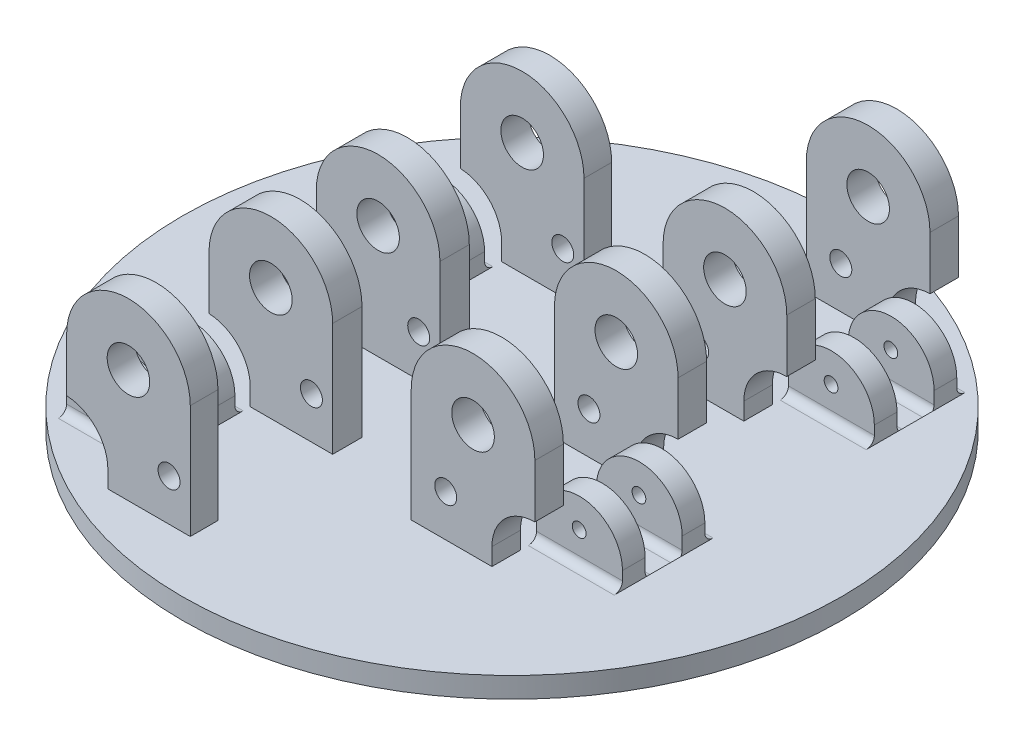
SolidWorks part; units mm, degrees
ref_plane "前视基准面" through (0, 0, 0) normal (0, 0, 1) x (1, 0, 0)
ref_plane "上视基准面" through (0, 0, 0) normal (0, 1, 0) x (1, 0, 0)
ref_plane "右视基准面" through (0, 0, 0) normal (1, 0, 0) x (0, 0, -1)
sketch "草图1" plane through (0, 0, 0) normal (0, 1, 0) x (1, 0, 0)
  line L4 (-45, -14.75) -> (46.6034, -14.75) construction
  circle A0 centre (-27, -5.58) radius 1
  circle A13 centre (-27, -42.25) radius 1
  circle A14 centre (27, 12.75) radius 1
  circle A15 centre (27, -23.92) radius 1
  circle A16 centre (0, -14.75) radius 48
  dimension "D13" = 36.67
  dimension "D14" = 2
  dimension "D16" = 2
  dimension "D2" = 27
  dimension "D15" = 2
  dimension "D17" = 2
  dimension "D6" = 18.34
  dimension "D3" = 27
  dimension "D4" = 27
  dimension "D5" = 27
  dimension "D7" = 9.17
extrude "凸台-拉伸1" add sketch "草图1" along normal blind 2.5 contours A14 A0 region at (0, 0, 14.75)
sketch "草图11" plane through (0, 2.5, 0) normal (0, 1, 0) x (1, 0, 0)
  line L1 (-25, 6.759) -> (-7, 6.759)
  line L2 (-25, 6.759) -> (-25, -18.241)
  line L3 (-25, -18.241) -> (-7, -18.241)
  line L4 (-7, 6.759) -> (-7, -18.241)
  line L5 (-25, -29.589) -> (-7, -29.589)
  line L6 (-25, -29.589) -> (-25, -54.589)
  line L7 (-25, -54.589) -> (-7, -54.589)
  line L8 (-7, -29.589) -> (-7, -54.589)
  line L9 (25, 25.25) -> (7, 25.25)
  line L10 (25, 25.25) -> (25, 0.25)
  line L11 (25, 0.25) -> (7, 0.25)
  line L12 (7, 25.25) -> (7, 0.25)
  line L13 (25, -11.42) -> (7, -11.42)
  line L14 (25, -11.42) -> (25, -36.42)
  line L15 (25, -36.42) -> (7, -36.42)
  line L16 (7, -11.42) -> (7, -36.42)
  line L17 (-25, 2.42) -> (-30, 2.42)
  line L18 (-25, 2.42) -> (-25, -13.58)
  line L19 (-25, -13.58) -> (-30, -13.58)
  line L20 (-30, 2.42) -> (-30, -13.58)
  line L21 (25, 20.75) -> (30, 20.75)
  line L22 (25, 20.75) -> (25, 4.75)
  line L23 (25, 4.75) -> (30, 4.75)
  line L24 (30, 20.75) -> (30, 4.75)
  line L25 (25, -15.92) -> (30, -15.92)
  line L26 (25, -15.92) -> (25, -31.92)
  line L27 (25, -31.92) -> (30, -31.92)
  line L28 (30, -15.92) -> (30, -31.92)
  line L29 (-25, -34.25) -> (-30, -34.25)
  line L30 (-25, -34.25) -> (-25, -50.25)
  line L31 (-25, -50.25) -> (-30, -50.25)
  line L32 (-30, -34.25) -> (-30, -50.25)
  circle A0 centre (-27, -5.58) radius 1 construction
  circle A1 centre (-27, -42.25) radius 1 construction
  circle A2 centre (27, -23.92) radius 1 construction
  circle A3 centre (27, 12.75) radius 1 construction
  dimension "D1" = 25
  dimension "D2" = 25
  dimension "D3" = 25
  dimension "D4" = 25
  dimension "D5" = 16
  dimension "D6" = 16
  dimension "D7" = 16
  dimension "D8" = 16
  dimension "D9" = 12.5
  dimension "D10" = 8
  dimension "D11" = 12.5
  dimension "D12" = 8
  dimension "D13" = 12.5
  dimension "D14" = 8
  dimension "D15" = 12.5
  dimension "D16" = 8
  dimension "D17" = 18
  dimension "D18" = 5
  dimension "D19" = 18
  dimension "D20" = 5
  dimension "D21" = 18
  dimension "D22" = 5
  dimension "D23" = 5
  dimension "D24" = 18
  dimension "D25" = 3
  dimension "D26" = 3
  dimension "D27" = 3
  dimension "D28" = 3
extrude "凸台-拉伸13" add sketch "草图11" along normal blind 26 contours L4 L1 L2 L3 | L9 L12 L11 L10 | L13 L16 L15 L14 | L8 L5 L6 L7 region at (-16, 2.5, 5.741) region at (-16, 2.5, 42.089) region at (16, 2.5, -12.75) region at (16, 2.5, 23.92)
sketch "草图12" plane through (0, 0, -6.759) normal (0, 0, -1) x (-1, 0, 0)
  line L0 (25, 19.5) -> (25, 11.745)
  line L1 (7, 28.5) -> (7, 2.5) construction
  line L2 (19, 2.5) -> (25, 2.5)
  line L3 (25, 28.5) -> (25, 2.5) construction
  line L4 (7, 19.5) -> (7, 2.5)
  line L5 (7, 2.5) -> (19, 2.5)
  line L6 (25, 11.745) -> (25, 19.5)
  line L7 (7, 2.5) -> (19, 2.5)
  line L8 (19, 2.5) -> (19, 5.5)
  line L10 (25, 2.5) -> (31.5, 2.5)
  line L11 (31.5, 2.5) -> (31.5, 5.5)
  arc A0 (7, 19.5) -> (25, 19.5) centre (16, 19.5) cw
  circle A1 centre (16, 19.5) radius 3.1
  arc A2 (19, 5.5) -> (31.5, 5.5) centre (25.25, 5.5) cw
  circle A3 centre (10.09, 9.09) radius 1.6
  line M2 (7, 2.5) -> (25, 2.5)
  line M3 (25, 2.5) -> (25, 28.5)
  line M4 (25, 28.5) -> (7, 28.5)
  line M5 (7, 28.5) -> (7, 2.5)
  dimension "D1" = 3
  dimension "D2" = 3.2
  dimension "D3" = 10.41
  dimension "D4" = 5.91
  dimension "D5" = 12
  dimension "D6" = 3
  dimension "D7" = 12.5
extrude "切除-拉伸19" cut sketch "草图12" against normal through all contours A0 M5 M4 region at (-9.0103, 26.4897, -6.759)
extrude "切除-拉伸23" cut sketch "草图12<9>" against normal blind 26 contours A0 M4 M3 region at (-22.9897, 26.4897, -6.759)
sketch "草图12<9>" plane through (0, 0, -6.759) normal (0, 0, -1) x (-1, 0, 0) same geometry as "草图12"
extrude "切除-拉伸24" cut sketch "草图12<10>" against normal through all contours A1 | A3 region at (-16, 19.5, -6.759) region at (-10.09, 9.09, -6.759)
sketch "草图12<10>" plane through (0, 0, -6.759) normal (0, 0, -1) x (-1, 0, 0) same geometry as "草图12"
extrude "切除-拉伸25" cut sketch "草图12<11>" against normal through all contours A2 L8 M2 M3 region at (-22.2854, 6.5506, -6.759)
sketch "草图12<11>" plane through (0, 0, -6.759) normal (0, 0, -1) x (-1, 0, 0) same geometry as "草图12"
sketch "草图13" plane through (0, 0, 54.589) normal (0, 0, 1) x (1, 0, 0)
  line L0 (-25, 28.5) -> (-25, 11.745) construction
  line L1 (-25, 19.5) -> (-25, 28.5)
  line L2 (-25, 28.5) -> (-16, 28.5)
  arc A0 (-16, 28.5) -> (-25, 19.5) centre (-16, 19.5) ccw
extrude "切除-拉伸26" cut sketch "草图13" against normal through all
sketch "草图16" plane through (-25, 0, 0) normal (-1, 0, 0) x (0, 0, 1)
  line L0 (5.6201, 10.245) -> (5.6201, 31.9219) construction
  line L1 (18.1201, 10.245) -> (-6.8799, 10.245) construction
  line L2 (18.241, 2.5) -> (-6.759, 2.5) construction
  line L3 (13.9701, 10.245) -> (13.9701, 31.9219)
  line L4 (13.9701, 31.9219) -> (-2.7299, 31.9219)
  line L5 (-2.7299, 31.9219) -> (-2.7299, 10.245)
  line L6 (13.9701, 2.5) -> (-2.7299, 2.5)
  line L7 (-2.7299, 10.245) -> (-2.7299, 2.5)
  line L9 (13.9701, 10.245) -> (13.9701, 2.5)
sketch "草图17" plane through (-25, 0, 0) normal (-1, 0, 0) x (0, 0, 1)
  line L1 (54.7099, 10.245) -> (29.7099, 10.245) construction
  line L3 (50.5599, 10.245) -> (50.5599, 33.0392)
  line L4 (50.5599, 33.0392) -> (33.8599, 33.0392)
  line L5 (33.8599, 33.0392) -> (33.8599, 10.245)
  line L8 (33.8599, 10.245) -> (33.8599, 2.5)
  line L9 (33.8599, 2.5) -> (50.5599, 2.5)
  line L10 (50.5599, 2.5) -> (50.5599, 10.245)
extrude "切除-拉伸31" cut sketch "草图17" against normal up to next
extrude "切除-拉伸30" cut sketch "草图16" against normal up to next
sketch "草图19" plane through (0, 0, -6.759) normal (0, 0, -1) x (-1, 0, 0)
  line L0 (19, 5.5) -> (19, 2.5)
  line L1 (31.5, 5.5) -> (31.5, 2.5)
  line L2 (31.5, 2.5) -> (19, 2.5)
  arc A0 (25, 11.745) -> (19, 5.5) centre (25.25, 5.5) ccw construction
  arc A1 (25, 11.745) -> (19, 5.5) centre (25.25, 5.5) ccw
  arc A2 (25, 11.745) -> (31.5, 5.5) centre (25.25, 5.5) cw
ref_plane "基准面1" through (0, 0, 5.741) normal (0, 0, -1) x (-1, 0, 0)
sketch "草图20" plane through (0, 0, 5.741) normal (0, 0, -1) x (-1, 0, 0)
  line L0 (31.5, 2.5) -> (19, 2.5) construction
  line L1 (31.5, 5.5) -> (31.5, 2.5) construction
  line L2 (19, 5.5) -> (19, 2.5) construction
  line L3 (31.5, 2.5) -> (19, 2.5)
  line L4 (31.5, 5.5) -> (31.5, 2.5)
  line L5 (19, 5.5) -> (19, 2.5)
  arc A0 (31.5, 5.5) -> (25, 11.745) centre (25.25, 5.5) ccw construction
  arc A1 (25, 11.745) -> (19, 5.5) centre (25.25, 5.5) ccw construction
  arc A2 (31.5, 5.5) -> (25, 11.745) centre (25.25, 5.5) ccw
  arc A3 (25, 11.745) -> (19, 5.5) centre (25.25, 5.5) ccw
  circle A4 centre (25.3145, 7.499) radius 1
  dimension "D1" = 2
extrude "凸台-拉伸18" add sketch "草图20" along normal mid plane 12
sketch "草图21" plane through (-31.5, 0, 0) normal (-1, 0, 0) x (0, 0, 1)
  line L0 (-0.259, 2.5) -> (11.741, 2.5) construction
  line L1 (8.4951, 2.5) -> (3.0951, 2.5)
  line L2 (8.4951, 2.5) -> (8.4951, 20.5257)
  line L3 (8.4951, 20.5257) -> (3.0951, 20.5257)
  line L4 (3.0951, 2.5) -> (3.0951, 20.5257)
  dimension "D1" = 5.4
extrude "切除-拉伸33" cut sketch "草图21" against normal up to next
ref_plane "基准面2" through (0, 0, 23.915) normal (0, 0, -1) x (-1, 0, 0)
mirror "镜向2" about plane through (0, 0, 23.915) normal (0, 0, -1) of "凸台-拉伸18"
mirror "镜向5" about plane through (0, 0, 23.915) normal (0, 0, -1) of "切除-拉伸33"
sketch "草图24" plane through (0, 0, -25.25) normal (0, 0, -1) x (-1, 0, 0)
  line L0 (-25, 28.5) -> (-25, 19.5)
  line L1 (-25, 28.5) -> (-25, 2.5) construction
  line L2 (-25, 19.5) -> (-25, 28.5)
  line L3 (-7, 28.5) -> (-7, 2.5) construction
  line L4 (-18.75, 5.5127) -> (-18.75, 2.5)
  line L7 (-7, 28.5) -> (-7, 19.5)
  line L11 (-25, 2.5) -> (-7, 2.5) construction
  line L12 (48, 2.5) -> (-48, 2.5) construction
  line L13 (-31.25, 5.5) -> (-31.25, 2.5)
  line L14 (-18.75, 2.5) -> (-31.25, 2.5)
  arc A0 (-25, 19.5) -> (-7, 19.5) centre (-16, 19.5) cw
  circle A1 centre (-16, 19.5) radius 3.1
  arc A2 (-31.25, 5.5) -> (-18.75, 5.5127) centre (-25, 5.5) cw
  circle A6 centre (-12.0207, 9.09) radius 1.6
  line M1 (-25, 2.5) -> (-7, 2.5)
  line M2 (-7, 2.5) -> (-7, 28.5)
  line M3 (-7, 28.5) -> (-25, 28.5)
  line M4 (-25, 28.5) -> (-25, 2.5)
  dimension "D1" = 3
  dimension "D3" = 6.25
extrude "切除-拉伸35" cut sketch "草图24" against normal through all contours A0 M4 M3 | A0 M3 M2 | A1 | A6 | A2 L4 M4 M1 region at (22.9897, 26.4897, -25.25) region at (9.0103, 26.4897, -25.25) region at (22.1682, 6.5774, -25.25) region at (16, 19.5, -25.25) region at (12.0207, 9.09, -25.25)
sketch "草图26" plane through (25, 0, 0) normal (1, 0, 0) x (0, 0, -1)
  line L0 (33.25, 2.5) -> (-62.75, 2.5) construction
  line L1 (-15.57, 2.5) -> (-32.27, 2.5)
  line L2 (-15.57, 2.5) -> (-15.57, 33.9045)
  line L3 (-15.57, 33.9045) -> (-32.27, 33.9045)
  line L4 (-32.27, 2.5) -> (-32.27, 33.9045)
  dimension "D1" = 16.7
extrude "切除-拉伸40" cut sketch "草图26" against normal up to surface (18 mm away) up to face at (7, 11, 23.92)
ref_plane "基准面5" through (0, 0, 23.92) normal (0, 0, -1) x (-1, 0, 0)
sketch "草图27" plane through (0, 0, 23.92) normal (0, 0, -1) x (-1, 0, 0)
  line L2 (-31.25, 5.5) -> (-31.25, 2.5)
  line L3 (-31.25, 2.5) -> (-18.75, 2.5)
  line L4 (-18.75, 2.5) -> (-18.75, 5.5127)
  line L9 (48, 2.5) -> (-48, 2.5) construction
  arc A1 (-18.75, 5.5127) -> (-25, 11.75) centre (-25, 5.5) ccw construction
  arc A2 (-18.75, 5.5127) -> (-25, 11.75) centre (-25, 5.5) ccw
  arc A3 (-25, 11.75) -> (-31.25, 5.5) centre (-25, 5.5) ccw
  circle A4 centre (-24.9508, 7.4994) radius 1
  circle A5 centre (-16, 19.5) radius 3.1
  circle A6 centre (-16, 19.5) radius 3.1
  dimension "D1" = 0
  dimension "D2" = 2
extrude "凸台-拉伸20" add sketch "草图27" along normal mid plane 12 contours L2 A4 region at (29.3095, 9.8095, 23.92)
sketch "草图28" plane through (33.4307, 0, 0) normal (1, 0, 0) x (0, 0, -1)
  line L0 (-23.92, 2.5) -> (-21.22, 2.5)
  line L1 (-17.92, 2.5) -> (-29.92, 2.5) construction
  line L2 (-26.62, 2.5) -> (-26.62, 12.9642)
  line L3 (-26.62, 12.9642) -> (-21.22, 12.9642)
  line L4 (-21.22, 12.9642) -> (-21.22, 2.5)
  line L5 (-26.62, 2.5) -> (-23.92, 2.5)
  dimension "D1" = 2.7
  dimension "D2" = 2.7
extrude "切除-拉伸41" cut sketch "草图28" against normal up to next
ref_plane "基准面6" through (0, 0, 5.585) normal (0, 0, -1) x (-1, 0, 0)
sketch "草图29" plane through (7, 0, 0) normal (-1, 0, 0) x (0, 0, 1)
  line L0 (-12.75, 19.5) -> (-12.75, 1.9724) construction
  line L1 (-0.25, 19.5) -> (-25.25, 19.5) construction
  line L2 (-12.75, 2.5) -> (-21.1, 2.5)
  line L3 (-25.25, 2.5) -> (-0.25, 2.5) construction
  line L4 (-21.1, 2.5) -> (-21.1, 15.8913)
  line L5 (-21.1, 15.8913) -> (-21.1, 43.9288)
  line L6 (-4.4, 15.8913) -> (-4.4, 2.5)
  line L7 (-25.25, 2.5) -> (-0.25, 2.5) construction
  line L8 (-4.4, 2.5) -> (-12.75, 2.5)
  line L9 (-21.1, 43.9288) -> (-4.4, 43.9288)
  line L10 (-4.4, 43.9288) -> (-4.4, 15.8913)
  dimension "D1" = 16.7
  dimension "D2" = 8.35
extrude "切除-拉伸42" cut sketch "草图29" against normal up to surface (18 mm away) up to face at (25, 15.625, -12.75)
mirror "镜向11" about plane through (0, 0, 5.585) normal (0, 0, -1) of "切除-拉伸41", "凸台-拉伸20"
sketch "草图34" plane through (0, 0, 0) normal (0, -1, 0) x (1, 0, 0)
  line L0 (0, 62.75) -> (0, -14.4275) construction
  line L1 (0, 14.75) -> (14.0338, 60.6526) construction
  line L2 (0, 14.75) -> (-14.0338, -31.1526) construction
  line L10 (0, 14.75) -> (0, 16.25)
  line L12 (0, 14.75) -> (-45.9026, 28.7838) construction
  line L19 (14.6833, 1.8953) -> (-19.3612, 12.3038)
  line L20 (14.6833, 1.8953) -> (15.5604, 4.7643)
  line L21 (-19.3612, 12.3038) -> (-18.4841, 15.1727)
  line L22 (15.5604, 4.7643) -> (-18.4841, 15.1727)
  line L23 (14.6833, 1.8953) -> (-18.4841, 15.1727) construction
  line L24 (-19.3612, 12.3038) -> (15.5604, 4.7643) construction
  line L25 (-28.1323, -16.3854) -> (5.9121, -26.7938)
  line L26 (-28.1323, -16.3854) -> (-29.0095, -19.2543)
  line L27 (5.9121, -26.7938) -> (5.035, -29.6627)
  line L28 (-29.0095, -19.2543) -> (5.035, -29.6627)
  line L29 (-28.1323, -16.3854) -> (5.035, -29.6627) construction
  line L30 (5.9121, -26.7938) -> (-29.0095, -19.2543) construction
  circle A0 centre (0, 14.75) radius 48 construction
  dimension "D1" = 17
  dimension "D2" = 7
  dimension "D3" = 1.5
  dimension "D4" = 30
  dimension "D5" = 35.6
  dimension "D6" = 3
  dimension "D8" = 35.6
  dimension "D9" = 3
extrude "凸台-拉伸21" add sketch "草图34" along normal blind 11.5 contours L20 L22 L21 L19 | L26 L28 L27 L25 region at (-1.9004, 0, 8.534) region at (-11.5487, 0, -23.024)
sketch "草图35" plane through (-7.8632, 0, -25.7193) normal (-0.2924, 0, -0.9563) x (-0.9563, 0, 0.2924)
  line L1 (22.1125, -11.5) -> (-13.4875, -11.5) construction
  line L2 (4.3125, -11.5) -> (4.3125, 0) construction
  line L3 (-13.4875, -11.5) -> (-13.4875, 0) construction
  line L4 (22.1125, 0) -> (-13.4875, 0) construction
  circle A0 centre (19.3125, -9.1) radius 1.4
  circle A1 centre (12.8125, -2.8) radius 1.4
  circle A4 centre (-4.1875, -2.8) radius 1.4
  circle A5 centre (-10.6875, -9.1) radius 1.4
  dimension "D1" = 2.8
  dimension "D2" = 2.8
  dimension "D3" = 6.3
  dimension "D4" = 6.5
extrude "切除-拉伸43" cut sketch "草图35" against normal through all
sketch "草图36" plane through (2.6622, 0, 8.7076) normal (0.2924, 0, 0.9563) x (0.9563, 0, -0.2924)
  line L0 (-10.6125, 0) -> (-10.6125, -5.6)
  line L1 (13.4875, 0) -> (-22.1125, 0) construction
  line L2 (-10.6125, -5.6) -> (-16.5125, -5.6)
  line L3 (-16.5125, -5.6) -> (-16.5125, -11.5)
  line L4 (13.4875, -11.5) -> (-22.1125, -11.5) construction
  line L5 (-4.3125, -11.5) -> (-4.3125, 0) construction
  line L6 (7.8875, -5.6) -> (7.8875, -11.5)
  line L7 (1.9875, -5.6) -> (7.8875, -5.6)
  line L8 (1.9875, 0) -> (1.9875, -5.6)
  line L9 (-10.6125, 0) -> (1.9875, 0)
  line L10 (-16.5125, -11.5) -> (7.8875, -11.5)
  circle A0 centre (-12.8125, -2.8) radius 1.4 construction
  circle A1 centre (-19.3125, -9.1) radius 1.4 construction
  dimension "D1" = 2.2
  dimension "D2" = 2.8
  dimension "D3" = 2.8
extrude "切除-拉伸44" cut sketch "草图36" against normal through all
sketch "草图37" plane through (0, 0, 0) normal (0, -1, 0) x (1, 0, 0)
  line L0 (-18.4841, 15.1727) -> (-29.0095, -19.2543)
  line L1 (-29.0095, -19.2543) -> (-30.7308, -18.728)
  line L2 (-30.7308, -18.728) -> (-20.2054, 15.699)
  line L3 (-20.2054, 15.699) -> (-18.4841, 15.1727)
  line L4 (5.035, -29.6627) -> (15.5604, 4.7643)
  line L5 (15.5604, 4.7643) -> (17.2817, 4.238)
  line L6 (17.2817, 4.238) -> (6.7563, -30.189)
  line L7 (6.7563, -30.189) -> (5.035, -29.6627)
  dimension "D1" = 1.8
  dimension "D2" = 1.8
extrude "凸台-拉伸22" add sketch "草图37" along normal blind 8
fillet "圆角9" radius 2 6 edges at (4.1243, -5.6, 6.6921) (9.7665, -5.6, 4.9671) (9.7665, -11.5, 4.9671) (-7.9251, -5.6, 10.376) (-13.5673, -5.6, 12.101) (-13.5673, -11.5, 12.101)
sketch "草图38" plane through (14.6195, 0, -4.4696) normal (0.9563, 0, -0.2924) x (-0.2924, 0, -0.9563)
  line L0 (-9.1055, -4) -> (26.8945, -4) construction
  line L1 (-9.1055, -8) -> (-9.1055, 0) construction
  line L2 (26.8945, -8) -> (26.8945, 0) construction
  line L3 (-0.7887, -4) -> (19.2113, -4) construction
  line L4 (-0.7887, -2.2) -> (19.2113, -2.2)
  line L5 (-0.7887, -5.8) -> (19.2113, -5.8)
  arc A0 (-0.7887, -2.2) -> (-0.7887, -5.8) centre (-0.7887, -4) ccw
  arc A1 (19.2113, -5.8) -> (19.2113, -2.2) centre (19.2113, -4) ccw
  point P8 (9.2113, -4)
  dimension "D2" = 1.8
  dimension "D1" = 20
extrude "切除-拉伸45" cut sketch "草图38" against normal up to next
fillet "圆角10" radius 2 6 edges at (-23.2156, -11.5, -19.4571) (-23.2156, -5.6, -19.4571) (-17.5734, -5.6, -21.1821) (-5.524, -5.6, -24.866) (0.1182, -5.6, -26.591) (0.1182, -11.5, -26.591)
sketch "草图39" plane through (-22.8676, 0, 6.9913) normal (-0.9563, 0, 0.2924) x (0.2924, 0, 0.9563)
  line L3 (6.1055, -8) -> (6.1055, 0)
  line L4 (9.1055, -8) -> (-26.8945, -8) construction
  line L5 (6.1055, 0) -> (-11.8945, 0)
  line L6 (-11.8945, 0) -> (-11.8945, -1.71)
  line L7 (-7.328, -8) -> (6.1055, -8)
  spline S0 degree 2 poles (-11.8945, -1.71) (-12.3537, -6.55) (-7.328, -8) knots 0 0 0 1 1 1
  dimension "D2" = 18
  dimension "D1" = 8
  dimension "D3" = 3
extrude "切除-拉伸46" cut sketch "草图39" against normal up to next
fillet "圆角12" radius 1.2 12 edges at (0.3969, 0, -28.2447) (-24.3714, 0, -20.6723) (-13.846, 0, 13.7547) (10.9223, 0, 6.1823) (-18.9226, -8, 13.7382) (12.019, 0, -12.9755) (-28.538, 0, -11.5557) (-28.5709, -8, -17.8198) (15.1218, -8, 3.3298) (5.4735, -8, -28.2283) (-5.524, 0, -24.866) (-17.5734, 0, -21.1821)
sketch "草图40" plane through (0, 2.5, 0) normal (0, 1, 0) x (1, 0, 0)
  line L1 (-31.5, -39.3349) -> (-19, -39.3349)
  line L2 (-31.5, -39.3349) -> (-31.5, -44.7349)
  line L3 (-31.5, -44.7349) -> (-19, -44.7349)
  line L4 (-19, -39.3349) -> (-19, -44.7349)
  line L5 (18.75, -21.22) -> (31.25, -21.22)
  line L6 (18.75, -21.22) -> (18.75, -26.62)
  line L7 (18.75, -26.62) -> (31.25, -26.62)
  line L8 (31.25, -21.22) -> (31.25, -26.62)
  line L9 (18.75, 15.45) -> (31.25, 15.45)
  line L10 (18.75, 15.45) -> (18.75, 10.05)
  line L11 (18.75, 10.05) -> (31.25, 10.05)
  line L12 (31.25, 15.45) -> (31.25, 10.05)
  line L13 (-31.5, -3.0951) -> (-19, -3.0951)
  line L14 (-31.5, -3.0951) -> (-31.5, -8.4951)
  line L15 (-31.5, -8.4951) -> (-19, -8.4951)
  line L16 (-19, -3.0951) -> (-19, -8.4951)
  circle A0 centre (0, -14.75) radius 48 construction
  circle A1 centre (0, -14.75) radius 48
extrude "凸台-拉伸23" add sketch "草图40" along normal blind 0.5
fillet "圆角13" radius 1.2 16 edges at (25, 3, -6.75) (25, 2.5, -10.05) (25, 2.5, -15.45) (25, 3, -18.75) (25, 3, 17.92) (25, 3, 29.92) (25, 2.5, 26.62) (25, 2.5, 21.22) (-25.25, 3, 48.089) (-25.25, 2.5, 44.7349) (-25.25, 3, 36.089) (-25.25, 2.5, 39.3349) (-25.25, 3, 11.741) (-25.25, 3, -0.259) (-25.25, 2.5, 8.4951) (-25.25, 2.5, 3.0951)
